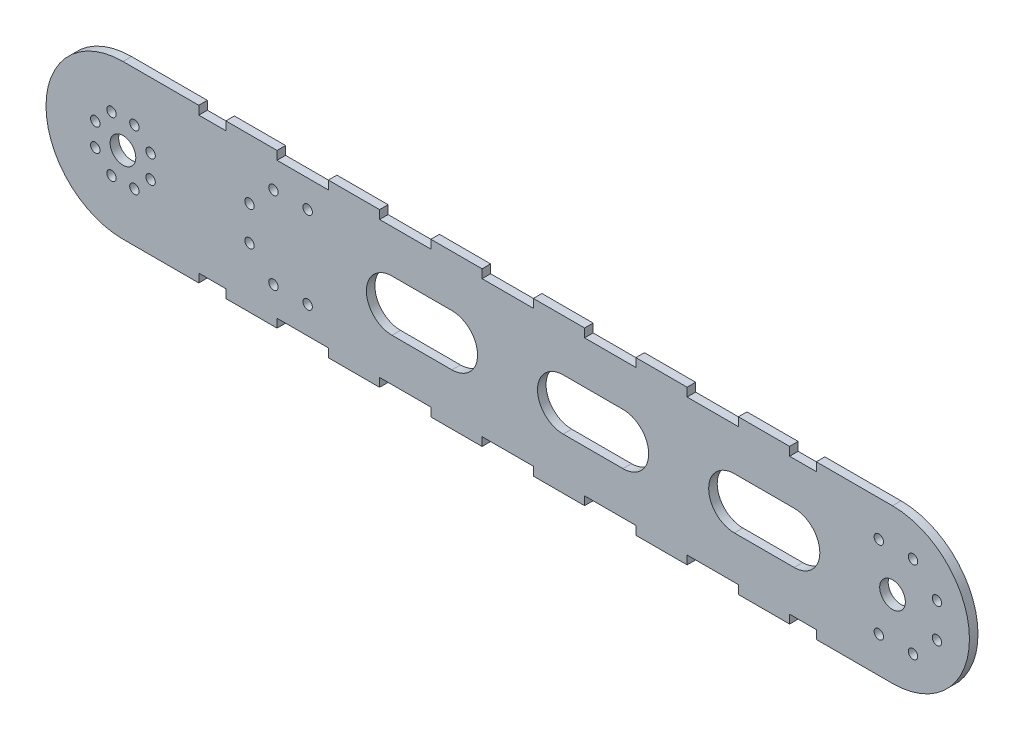
SolidWorks part; units mm, degrees
ref_plane "Front Plane" through (0, 0, 0) normal (0, 0, 1) x (1, 0, 0)
ref_plane "Top Plane" through (0, 0, 0) normal (0, 1, 0) x (1, 0, 0)
ref_plane "Right Plane" through (0, 0, 0) normal (1, 0, 0) x (0, 0, -1)
sketch "Sketch3" plane through (0, 0, 0) normal (0, 0, 1) x (1, 0, 0)
  line L0 (-242.5, 0) -> (207.5, 0) construction
  line L1 (-242.5, 45) -> (207.5, 45)
  line L2 (-242.5, -45) -> (207.5, -45)
  line L3 (-152.388, 45) -> (-122.388, 45)
  line L6 (115, 0) -> (150, 0) construction
  line L7 (115, 15) -> (150, 15)
  line L8 (115, -15) -> (150, -15)
  line L9 (-242.5, 0) -> (-226.3321, 6.697)
  line L10 (-242.5, 0) -> (-226.3321, 6.697) construction
  line L11 (-242.5, 0) -> (-226.3321, -6.697) construction
  line L36 (-101.4371, 0) -> (436.7316, 0) construction
  line L45 (27.444, 45) -> (57.444, 45)
  line L46 (57.444, 45) -> (57.444, 40)
  line L47 (27.444, 40) -> (57.444, 40)
  line L48 (27.444, 45) -> (27.444, 40)
  line L49 (-32.5, 40) -> (-2.5, 40)
  line L50 (-2.5, 45) -> (-2.5, 40)
  line L51 (-32.5, 45) -> (-2.5, 45)
  line L52 (-32.5, 45) -> (-32.5, 40)
  line L53 (-92.444, 45) -> (-62.444, 45)
  line L54 (-62.444, 45) -> (-62.444, 40)
  line L55 (-92.444, 40) -> (-62.444, 40)
  line L56 (-92.444, 45) -> (-92.444, 40)
  line L61 (-122.388, 45) -> (-122.388, 40)
  line L62 (-152.388, 40) -> (-122.388, 40)
  line L63 (-152.388, 45) -> (-152.388, 40)
  line L64 (-212.332, 45) -> (-182.332, 45)
  line L65 (-198.1549, 40) -> (-198.1549, 45)
  line L66 (162.9337, 40) -> (162.9337, 45)
  line L67 (-182.332, 45) -> (-182.332, 40)
  line L69 (32.5, 45) -> (32.5, -45) construction
  line L72 (-212.332, 40) -> (-182.332, 40)
  line L74 (14.924, 0) -> (49.924, 0) construction
  line L75 (14.924, 15) -> (49.924, 15)
  line L78 (14.924, -15) -> (49.924, -15)
  line L79 (-85.152, 0) -> (-50.152, 0) construction
  line L80 (-85.152, 15) -> (-50.152, 15)
  line L81 (-85.152, -15) -> (-50.152, -15)
  line L82 (-212.332, 45) -> (-212.332, 40)
  line L83 (87.388, 45) -> (117.388, 45)
  line L84 (117.388, 45) -> (117.388, 40)
  line L85 (87.388, 40) -> (117.388, 40)
  line L86 (87.388, 45) -> (87.388, 40)
  line L87 (147.332, 45) -> (177.332, 45)
  line L88 (177.332, 45) -> (177.332, 40)
  line L89 (147.332, 40) -> (177.332, 40)
  line L90 (147.332, 45) -> (147.332, 40)
  line L91 (-287.5, 0) -> (-17.5, 0) construction
  arc A0 (-242.5, 45) -> (-242.5, -45) centre (-242.5, 0) ccw
  arc A1 (207.5, -45) -> (207.5, 45) centre (207.5, 0) ccw
  circle A2 centre (-242.5, 0) radius 7.5
  circle A3 centre (207.5, 0) radius 7.5
  arc A6 (115, 15) -> (115, -15) centre (115, 0) ccw
  arc A7 (150, -15) -> (150, 15) centre (150, 0) ccw
  circle A8 centre (-226.3321, 6.697) radius 2.75
  circle A9 centre (-226.3321, -6.697) radius 2.75
  circle A10 centre (-235.803, -16.1679) radius 2.75
  circle A11 centre (-249.197, -16.1679) radius 2.75
  circle A12 centre (-258.6679, -6.697) radius 2.75
  circle A13 centre (-258.6679, 6.697) radius 2.75
  circle A14 centre (-249.197, 16.1679) radius 2.75
  circle A15 centre (-235.803, 16.1679) radius 2.75
  circle A41 centre (-134.5, -24) radius 2.75
  circle A42 centre (-154.5, -24) radius 2.75
  circle A43 centre (-168.5, -10) radius 2.75
  circle A44 centre (-168.5, 10) radius 2.75
  circle A45 centre (-154.5, 24) radius 2.75
  circle A46 centre (-134.5, 24) radius 2.75
  arc A49 (14.924, 15) -> (14.924, -15) centre (14.924, 0) ccw
  arc A50 (49.924, -15) -> (49.924, 15) centre (49.924, 0) ccw
  arc A51 (-85.152, 15) -> (-85.152, -15) centre (-85.152, 0) ccw
  arc A52 (-50.152, -15) -> (-50.152, 15) centre (-50.152, 0) ccw
  circle A53 centre (199.5, -24) radius 2.75
  circle A54 centre (219.5, -24) radius 2.75
  circle A55 centre (233.5, -10) radius 2.75
  circle A56 centre (233.5, 10) radius 2.75
  circle A57 centre (219.5, 24) radius 2.75
  circle A58 centre (199.5, 24) radius 2.75
  point P3 (-17.5, 0)
  point P19 (132.5, 0)
  point P68 (32.424, 0)
  point P75 (-67.652, 0)
  dimension "D2" = 45
  dimension "D3" = 15
  dimension "D4" = 15
  dimension "D7" = 5.5
  dimension "D27" = 15
  dimension "D1" = 450
  dimension "D5" = 17.5
  dimension "D6" = 22.5
  dimension "D9" = 45
  dimension "D10" = 3
  dimension "D11" = 3
  dimension "D15" = 3
  dimension "D26" = 35
  dimension "D29" = 150
  dimension "D30" = 175
  dimension "D8" = 8
extrude "Boss-Extrude1" add sketch "Sketch3" along normal blind 5 contours L2 A1 L1 L46 L47 L48 L50 L49 L52 L54 L55 L56 A0 | L87 L88 L89 L90 | L83 L84 L85 L86 | L45 L46 L47 L48 | L49 L50 L51 L52 | L64 L67 L72 L82 | L3 L61 L62 L63 | L53 L54 L55 L56 region at (-23.4079, -1.1237, 0)
extrude "Cut-Extrude1" cut sketch "Sketch3<3>" along normal through all contours L65 L72 L67 L64 | L1 L63 L62 L61 | L1 L56 L55 L54 | L1 L52 L49 L50 | L1 L48 L47 L46 | L1 L86 L85 L84 | L1 L90 L89 L66 region at (-190.2434, 42.5, 0) region at (-137.388, 42.5, 0) region at (155.1328, 42.5, 0) region at (-77.444, 42.5, 0) region at (102.388, 42.5, 0) region at (-17.5, 42.5, 0) region at (42.444, 42.5, 0)
sketch "Sketch3<3>" plane through (0, 0, 0) normal (0, 0, 1) x (1, 0, 0) same geometry as "Sketch3"
mirror "Mirror1" about plane through (0, 0, 0) normal (0, 1, 0) of "Cut-Extrude1"
